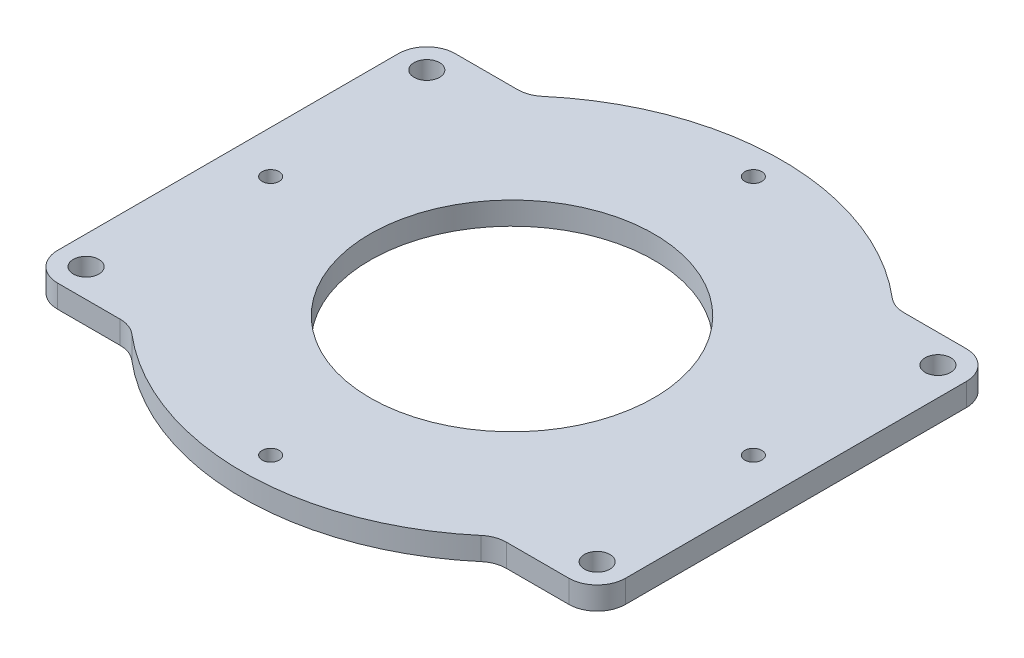
SolidWorks part; units mm, degrees
ref_plane "Front Plane" through (0, 0, 0) normal (0, 0, 1) x (1, 0, 0)
ref_plane "Top Plane" through (0, 0, 0) normal (0, 1, 0) x (1, 0, 0)
ref_plane "Right Plane" through (0, 0, 0) normal (1, 0, 0) x (0, 0, -1)
sketch "Sketch1" plane through (0, 0, 0) normal (0, 1, 0) x (1, 0, 0)
  line L0 (0, 0) -> (0, 42.5) construction
  line L1 (45, -30) -> (-45, -30) construction
  line L2 (45, -30) -> (45, 30) construction
  line L3 (45, 30) -> (-45, 30) construction
  line L4 (-45, -30) -> (-45, 30) construction
  line L5 (45, -30) -> (-45, 30) construction
  line L6 (45, 30) -> (-45, -30) construction
  line L7 (45, -35) -> (-45, -35) construction
  line L8 (50, -30) -> (50, 30)
  line L9 (45, 35) -> (-45, 35) construction
  line L10 (-50, -30) -> (-50, 30)
  line L11 (50, -35) -> (-50, 35) construction
  line L12 (50, 35) -> (-50, -35) construction
  line L13 (0, 0) -> (42.5, 0) construction
  line L14 (-45, 35) -> (-34.0037, 35)
  line L15 (34.0037, 35) -> (45, 35)
  line L16 (34.0037, -35) -> (45, -35)
  line L17 (-45, -35) -> (-34.0037, -35)
  circle A0 centre (-45, 30) radius 2.25
  circle A1 centre (-45, -30) radius 2.25
  circle A2 centre (45, -30) radius 2.25
  circle A3 centre (45, 30) radius 2.25
  circle A4 centre (0, 0) radius 25
  arc A5 (-50, -30) -> (-45, -35) centre (-45, -30) ccw
  arc A6 (45, -35) -> (50, -30) centre (45, -30) ccw
  arc A7 (50, 30) -> (45, 35) centre (45, 30) ccw
  arc A8 (-45, 35) -> (-50, 30) centre (-45, 30) ccw
  circle A9 centre (0, 0) radius 42.5 construction
  circle A10 centre (0, 42.5) radius 1.5
  circle A11 centre (42.5, 0) radius 1.5
  circle A12 centre (0, -42.5) radius 1.5
  circle A13 centre (-42.5, 0) radius 1.5
  arc A14 (30.7652, 36.1905) -> (-30.7652, 36.1905) centre (0, 0) ccw
  arc A15 (34.0037, 35) -> (30.7652, 36.1905) centre (34.0037, 40) cw
  arc A16 (-30.7652, 36.1905) -> (-34.0037, 35) centre (-34.0037, 40) cw
  arc A17 (34.0037, -35) -> (30.7652, -36.1905) centre (34.0037, -40) ccw
  arc A18 (30.7652, -36.1905) -> (-30.7652, -36.1905) centre (0, 0) cw
  arc A19 (-30.7652, -36.1905) -> (-34.0037, -35) centre (-34.0037, -40) ccw
  point P0 (0, 0)
  point P41 (32.1131, 35)
  point P44 (-32.1131, 35)
  dimension "D1" = 4.5
  dimension "D4" = 50
  dimension "D7" = 5
  dimension "D8" = 85
  dimension "D9" = 3
  dimension "D10" = 5
  dimension "D11" = 5
  dimension "D2" = 90
  dimension "D3" = 60
  dimension "D5" = 5
  dimension "D6" = 5
extrude "Boss-Extrude1" add sketch "Sketch1" along normal blind 4
